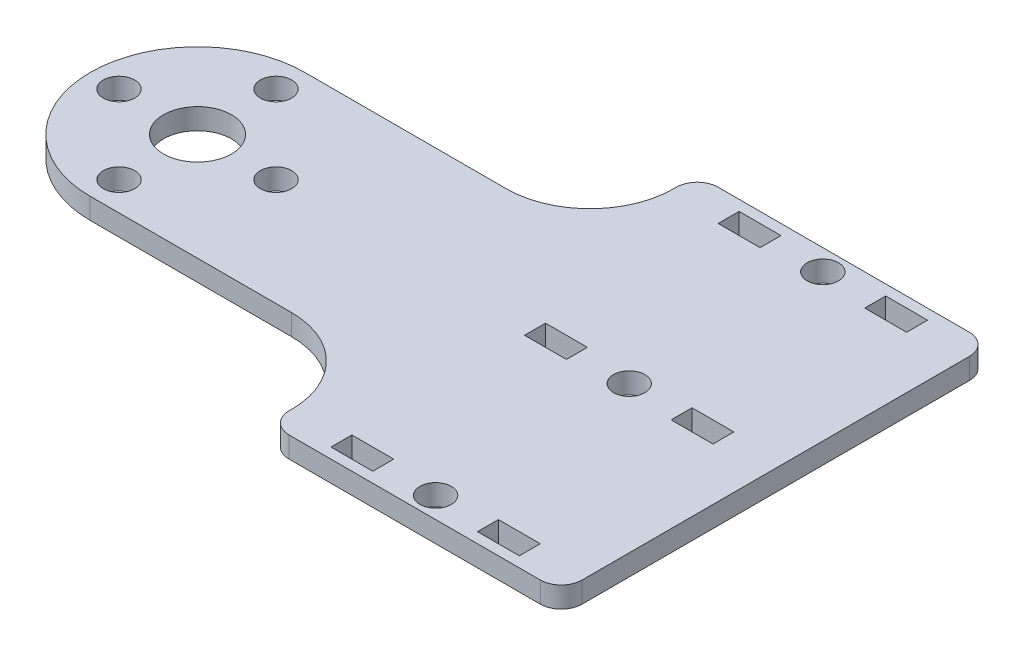
SolidWorks part; units mm, degrees
ref_plane "Front Plane" through (0, 0, 0) normal (0, 0, 1) x (1, 0, 0)
ref_plane "Top Plane" through (0, 0, 0) normal (0, 1, 0) x (1, 0, 0)
ref_plane "Right Plane" through (0, 0, 0) normal (1, 0, 0) x (0, 0, -1)
sketch "Sketch1" plane through (0, 0, 0) normal (0, 1, 0) x (1, 0, 0)
  line L0 (0, 10.25) -> (65.5, 10.25) construction
  line L1 (0, 0) -> (37.5, 0)
  line L2 (0, 0) -> (0, 20.5)
  line L3 (0, 20.5) -> (37.5, 20.5)
  line L4 (65.5, -0.75) -> (65.5, 21.25)
  line L5 (10.25, 10.25) -> (10.25, 20.5) construction
  line L6 (10.25, 10.25) -> (1.2579, 19.2421) construction
  line L7 (10.25, 10.25) -> (1.2579, 1.2579) construction
  line L8 (37.5, 0) -> (37.5, -10.25)
  line L10 (65.5, 21.25) -> (65.5, 30.75)
  line L11 (65.5, 30.75) -> (37.5, 30.75)
  line L12 (37.5, 20.5) -> (37.5, 30.75)
  line L13 (65.5, -10.25) -> (37.5, -10.25)
  line L14 (65.5, -0.75) -> (65.5, -10.25)
  circle A0 centre (10.25, 10.25) radius 3.25
  circle A1 centre (2.75, 10.25) radius 1.5
  circle A2 centre (10.25, 17.75) radius 1.5
  circle A3 centre (17.75, 10.25) radius 1.5
  circle A4 centre (10.25, 2.75) radius 1.5
  dimension "D1" = 3
  dimension "D2" = 7.5
  dimension "D3" = 6.5
  dimension "D4" = 20.5
  dimension "D5" = 10.25
  dimension "D6" = 55.25
  dimension "D7" = 41
  dimension "D8" = 28
extrude "Boss-Extrude1" add sketch "Sketch1" along normal blind 2
fillet "Fillet1" radius 10.25 2 edges at (0, 1, -20.5) (0, 1, 0)
fillet "Fillet2" radius 2 4 edges at (37.5, 1, -30.75) (65.5, 1, -30.75) (65.5, 1, 10.25) (37.5, 1, 10.25)
sketch "Sketch2" plane through (0, 2, 0) normal (0, 1, 0) x (1, 0, 0)
  line L0 (65.5, 10.25) -> (0, 10.25) construction
  line L1 (65.5, -8.25) -> (65.5, 28.75) construction
  line L2 (37.5, 28.75) -> (65.5, 28.75) construction
  line L3 (37.5, 28.75) -> (37.5, 20.5) construction
  line L15 (63.5, 30.75) -> (39.5, 30.75) construction
  line L17 (42.5, 27.75) -> (46.5, 27.75)
  line L18 (42.5, 27.75) -> (42.5, 29.75)
  line L19 (42.5, 29.75) -> (46.5, 29.75)
  line L20 (46.5, 27.75) -> (46.5, 29.75)
  line L21 (42.5, 27.75) -> (46.5, 29.75) construction
  line L22 (42.5, 29.75) -> (46.5, 27.75) construction
  line L23 (60.5, 27.75) -> (56.5, 27.75)
  line L24 (60.5, 27.75) -> (60.5, 29.75)
  line L25 (60.5, 29.75) -> (56.5, 29.75)
  line L26 (56.5, 27.75) -> (56.5, 29.75)
  line L27 (60.5, 27.75) -> (56.5, 29.75) construction
  line L28 (60.5, 29.75) -> (56.5, 27.75) construction
  line L37 (42.5, 9.25) -> (42.5, 11.25)
  line L38 (42.5, 9.25) -> (46.5, 9.25)
  line L39 (46.5, 9.25) -> (46.5, 11.25)
  line L40 (42.5, 11.25) -> (46.5, 11.25)
  line L41 (60.5, 9.25) -> (60.5, 11.25)
  line L42 (60.5, 9.25) -> (56.5, 9.25)
  line L43 (56.5, 9.25) -> (56.5, 11.25)
  line L44 (60.5, 11.25) -> (56.5, 11.25)
  line L53 (42.5, -9.25) -> (42.5, -7.25)
  line L54 (42.5, -9.25) -> (46.5, -9.25)
  line L55 (46.5, -9.25) -> (46.5, -7.25)
  line L56 (42.5, -7.25) -> (46.5, -7.25)
  line L57 (60.5, -9.25) -> (60.5, -7.25)
  line L58 (60.5, -9.25) -> (56.5, -9.25)
  line L59 (56.5, -9.25) -> (56.5, -7.25)
  line L60 (60.5, -7.25) -> (56.5, -7.25)
  circle A3 centre (51.5, 28.75) radius 1.5
  circle A4 centre (51.5, 10.25) radius 1.5
  circle A5 centre (51.5, -8.25) radius 1.5
  point P9 (26.5, 28.75)
  point P10 (58.5, 29.75)
  point P14 (35.5, 28.75)
  point P19 (44.5, 28.75)
  point P24 (58.5, 28.75)
  dimension "D11" = 3
  dimension "D12" = 5
  dimension "D2" = 4
  dimension "D3" = 1
  dimension "D5" = 5
  dimension "D6" = 10
  dimension "D8" = 3
extrude "Cut-Extrude1" cut sketch "Sketch2" against normal blind 2
fillet "Fillet3" radius 8 2 edges at (37.5, 1, 0) (37.5, 1, -20.5)
